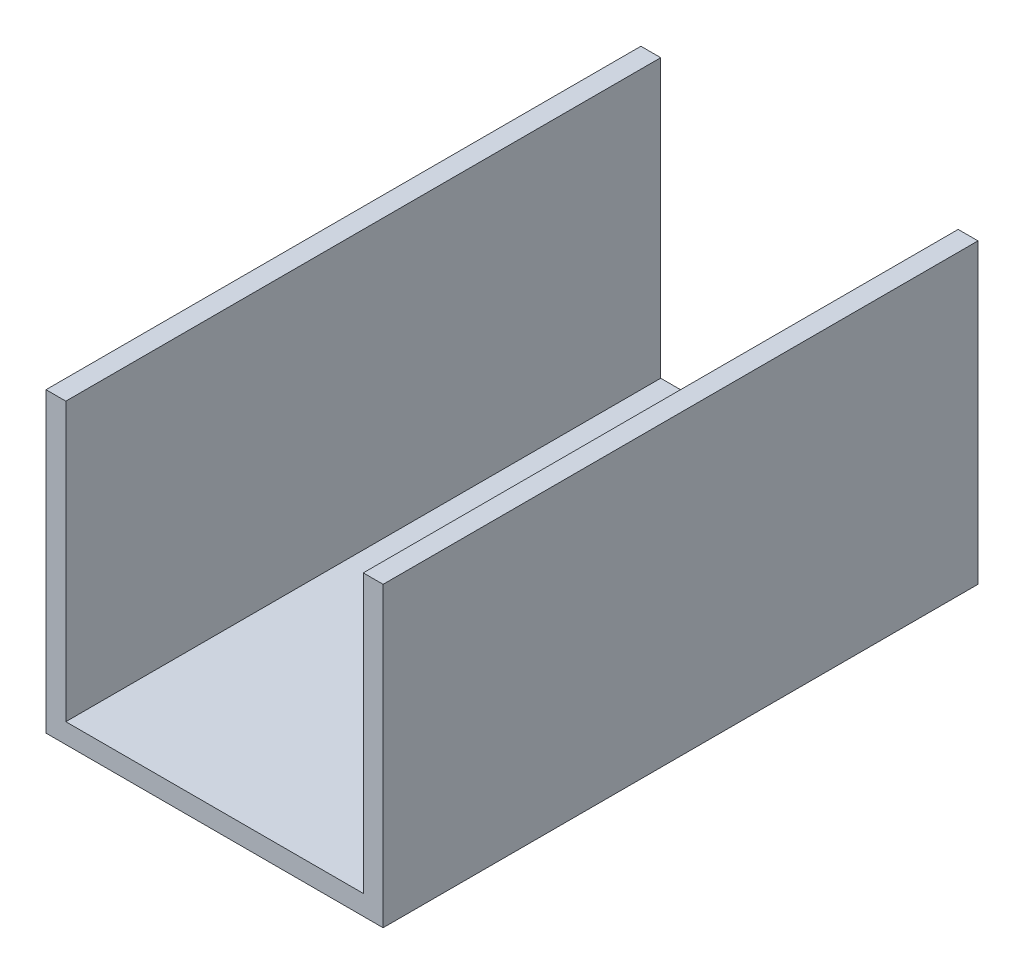
SolidWorks part; units mm, degrees
material "PLA"
ref_plane "Front Plane" through (0, 0, 0) normal (0, 0, 1) x (1, 0, 0)
ref_plane "Top Plane" through (0, 0, 0) normal (0, 1, 0) x (1, 0, 0)
ref_plane "Right Plane" through (0, 0, 0) normal (1, 0, 0) x (0, 0, -1)
sketch "Sketch2" plane through (0, 0, 0) normal (0, 0, 1) x (1, 0, 0)
  line L0 (-30, 0) -> (30, 0)
  line L1 (-30, 0) -> (-30, 56)
  line L2 (-30, 56) -> (-34, 56)
  line L3 (-34, 56) -> (-34, -4)
  line L7 (30, 56) -> (30, 0)
  line L8 (-34, -4) -> (34, -4)
  line L9 (34, -4) -> (34, 56)
  line L10 (34, 56) -> (30, 56)
  point P4 (0, 0)
  dimension "D1" = 60
  dimension "D2" = 4
  dimension "D3" = 4
  dimension "D4" = 60
  dimension "D5" = 4
  dimension "D6" = 60
extrude "Boss-Extrude1" add sketch "Sketch2" along normal mid plane 120
